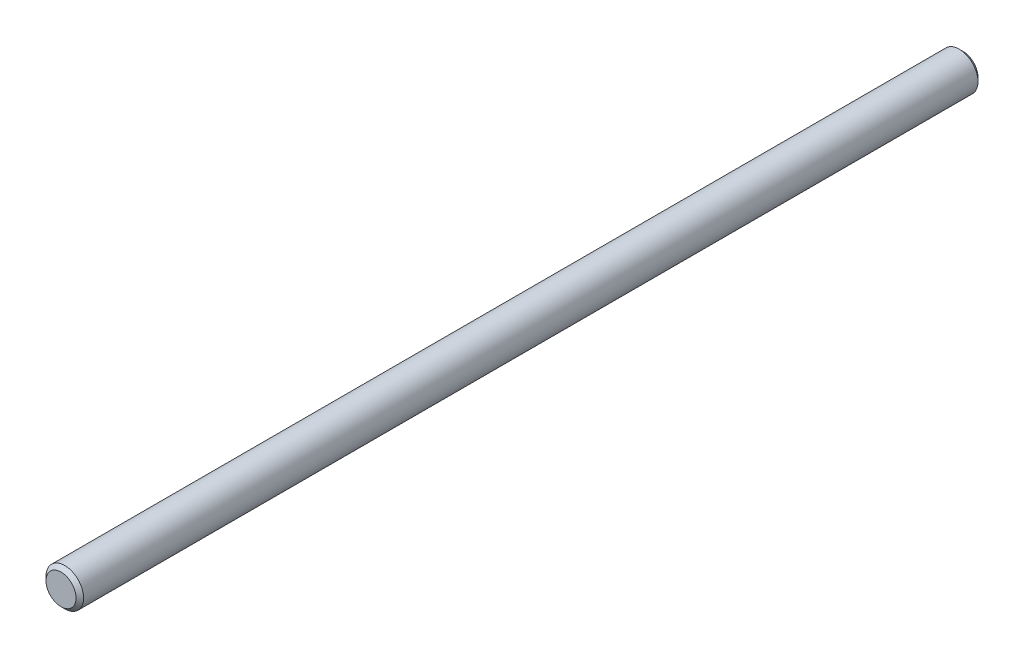
SolidWorks part; units mm, degrees
material "Arm 2 shaft metal"
ref_plane "Front" through (0, 0, 0) normal (0, 0, 1) x (1, 0, 0)
ref_plane "Top" through (0, 0, 0) normal (0, 1, 0) x (1, 0, 0)
ref_plane "Right" through (0, 0, 0) normal (1, 0, 0) x (0, 0, -1)
sketch "Sketch1" plane through (0, 0, 0) normal (0, 0, 1) x (1, 0, 0)
  circle A0 centre (0, 0) radius 1.5875
  dimension "dia" = 3.175
sketch "Sketch2" plane through (0, 0, 0) normal (1, 0, 0) x (0, 0, -1)
  line L0 (-38.1, 0) -> (38.1, 0) construction
  line L1 (55, 0) -> (-55, 0) construction
  line L3 (38.1, 1.5875) -> (38.1, -1.5875) construction
  line L4 (-38.1, 1.5875) -> (-38.1, -1.5875) construction
  line L5 (-19.05, 1.5875) -> (-19.05, -1.5875) construction
  line L6 (19.05, 1.5875) -> (19.05, -1.5875) construction
  point P6 (0, 0)
  point P10 (38.1, 0)
  point P13 (-38.1, 0)
  point P16 (-19.05, 0)
  point P19 (19.05, 0)
  dimension "D1" = 3.175
  dimension "lg" = 76.2
  dimension "D2" = 19.05
  dimension "D3" = 19.05
sketch "Sketch3" plane through (0, 0, 0) normal (0, 0, 1) x (1, 0, 0)
  line L0 (0, 1.5875) -> (0, -1.5875) construction
  circle A0 centre (0, 0) radius 1.5875
  dimension "D1" = 3.175
extrude "Boss-Extrude1" add sketch "Sketch3" along normal mid plane 76.2
chamfer "Chamfer1" distance 0.3175 angle 45 2 edges at (1.5875, 0, -38.1) (1.5875, 0, 38.1)
equation "\"D1@Sketch2\"=\"dia@sketch1\""
equation "\"D1@Sketch3\"=\"dia@Sketch1\""
equation "\"D1@Boss-Extrude1\"=\"lg@Sketch2\""
equation "\"D1@Chamfer1\"=\"dia@Sketch1\"*.1"
